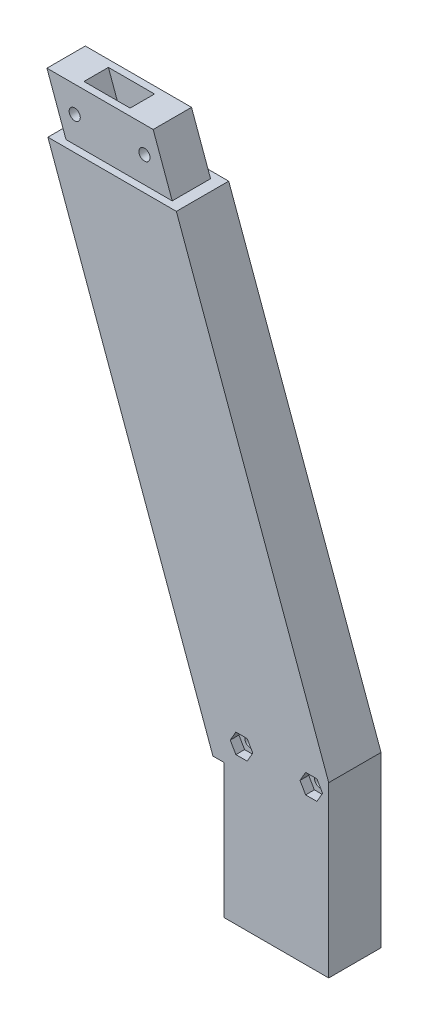
SolidWorks part; units mm, degrees
ref_plane "Front Plane" through (0, 0, 0) normal (0, 0, 1) x (1, 0, 0)
ref_plane "Top Plane" through (0, 0, 0) normal (0, 1, 0) x (1, 0, 0)
ref_plane "Right Plane" through (0, 0, 0) normal (1, 0, 0) x (0, 0, -1)
sketch "Sketch3" plane through (0, 0, 0) normal (0, 0, 1) x (1, 0, 0)
  line L1 (-127.0377, 609.9404) -> (92.9623, 609.9404)
  line L2 (-127.0377, 609.9404) -> (-127.0377, 389.9404)
  line L3 (-127.0377, 389.9404) -> (92.9623, 389.9404)
  line L4 (92.9623, 609.9404) -> (92.9623, 389.9404)
  dimension "D1" = 220
  dimension "D2" = 220
sketch "Sketch1" plane through (0, 0, 0) normal (0, 0, 1) x (1, 0, 0)
  line L0 (5, 40.95) -> (25, 40.95)
  line L1 (0, 0) -> (30, 0)
  line L2 (0, 0) -> (0, 34.5)
  line L3 (0, 34.5) -> (30, 34.5)
  line L4 (30, 0) -> (30, 34.5)
  line L5 (0, 0) -> (30, 0)
  line L6 (0, 0) -> (0, -4)
  line L7 (0, -4) -> (30, -4)
  line L8 (30, 0) -> (30, -4)
  line L9 (0, 34.5) -> (30, 34.5)
  line L10 (0, 34.5) -> (0, 44.5)
  line L11 (0, 44.5) -> (30, 44.5)
  line L12 (30, 34.5) -> (30, 44.5)
  line L14 (8.2332, 40.95) -> (6.6166, 43.75)
  line L15 (6.6166, 43.75) -> (3.3834, 43.75)
  line L16 (3.3834, 43.75) -> (1.7668, 40.95)
  line L17 (1.7668, 40.95) -> (3.3834, 38.15)
  line L18 (3.3834, 38.15) -> (6.6166, 38.15)
  line L19 (6.6166, 38.15) -> (8.2332, 40.95)
  line L20 (21.7668, 40.95) -> (23.3834, 38.15)
  line L21 (23.3834, 38.15) -> (26.6166, 38.15)
  line L22 (26.6166, 38.15) -> (28.2332, 40.95)
  line L23 (28.2332, 40.95) -> (26.6166, 43.75)
  line L24 (26.6166, 43.75) -> (23.3834, 43.75)
  line L25 (23.3834, 43.75) -> (21.7668, 40.95)
  circle A0 centre (15, 8) radius 6.5
  circle A1 centre (5, 40.95) radius 1.55
  circle A2 centre (25, 40.95) radius 1.55
  circle A3 centre (5, 40.95) radius 2.8 construction
  circle A4 centre (25, 40.95) radius 2.8 construction
  point P10 (15, 0)
  point P16 (5, 42.5)
  point P17 (5, 39.4)
  point P18 (15, 40.95)
  point P19 (15, 34.5)
  dimension "D4" = 13
  dimension "D7" = 3.1
  dimension "D10" = 5.6
  dimension "D1" = 30
  dimension "D2" = 34.5
  dimension "D3" = 4
  dimension "D5" = 8
  dimension "D6" = 20
  dimension "D8" = 4.9
  dimension "D9" = 2
sketch "Sketch2" plane through (0, 0, 0) normal (0, 0, 1) x (1, 0, 0)
  line L0 (0, 34.5) -> (-53.8676, 182.5)
  line L1 (-53.8676, 182.5) -> (-53.8676, 34.5)
  line L2 (-53.8676, 34.5) -> (0, 34.5)
  line L3 (30, 44.5) -> (-82.8834, 354.6447)
  line L4 (-82.8834, 354.6447) -> (-119.7157, 354.6447)
  line L5 (-119.7157, 354.6447) -> (-3.1925, 34.5)
  line L6 (-53.8676, 182.5) -> (-115.4312, 351.6447)
  line L7 (-55.9682, 179.5) -> (-19.136, 179.5)
  line L8 (-50.5087, 164.5) -> (-13.6764, 164.5)
  line L9 (-44.8223, 172) -> (-24.8223, 172)
  line L10 (-24.8223, 168.7668) -> (-22.0223, 170.3834)
  line L11 (-22.0223, 170.3834) -> (-22.0223, 173.6166)
  line L12 (-22.0223, 173.6166) -> (-24.8223, 175.2332)
  line L13 (-24.8223, 175.2332) -> (-27.6223, 173.6166)
  line L14 (-27.6223, 173.6166) -> (-27.6223, 170.3834)
  line L15 (-27.6223, 170.3834) -> (-24.8223, 168.7668)
  line L16 (-44.8223, 168.7668) -> (-42.0223, 170.3834)
  line L17 (-42.0223, 170.3834) -> (-42.0223, 173.6166)
  line L18 (-42.0223, 173.6166) -> (-44.8223, 175.2332)
  line L19 (-44.8223, 175.2332) -> (-47.6223, 173.6166)
  line L20 (-47.6223, 173.6166) -> (-47.6223, 170.3834)
  line L21 (-47.6223, 170.3834) -> (-44.8223, 168.7668)
  line L22 (-37.5521, 179.5) -> (-32.0925, 164.5)
  line L23 (-22.3285, 179.5) -> (-16.869, 164.5)
  line L24 (-52.7757, 179.5) -> (-47.3161, 164.5)
  line L25 (-44.1637, 179.5) -> (4.9723, 44.5)
  line L26 (0, 44.5) -> (30, 44.5) construction
  line L27 (-30.9405, 179.5) -> (18.1955, 44.5)
  line L28 (4.9723, 44.5) -> (18.1955, 44.5)
  line L29 (-44.1637, 179.5) -> (-30.9405, 179.5)
  line L30 (18.1955, 44.5) -> (30, 44.5)
  line L31 (4.9723, 44.5) -> (0, 44.5)
  line L32 (0, 44.5) -> (0, 34.5)
  circle A0 centre (-53.8676, 182.5) radius 2.5
  circle A1 centre (-66.1803, 216.3289) radius 2.5
  circle A2 centre (-78.493, 250.1579) radius 2.5
  circle A3 centre (-90.8058, 283.9868) radius 2.5
  circle A4 centre (-103.1185, 317.8157) radius 2.5
  circle A5 centre (-115.4312, 351.6447) radius 2.5
  circle A6 centre (-115.4312, 351.6447) radius 3
  circle A7 centre (-53.8676, 182.5) radius 3
  circle A8 centre (-24.8223, 172) radius 2.8 construction
  circle A9 centre (-44.8223, 172) radius 2.8 construction
  circle A10 centre (-44.8223, 172) radius 1.6
  circle A11 centre (-24.8223, 172) radius 1.6
  point P44 (-34.8223, 172)
  point P45 (-34.8223, 172)
  dimension "D3" = 5
  dimension "D5" = 6
  dimension "D8" = 5.6
  dimension "D10" = 3.2
  dimension "D1" = 148
  dimension "D2" = 70
  dimension "D6" = 180
  dimension "D7" = 15
  dimension "D9" = 20
  dimension "D11" = 3
  dimension "D12" = 3
  dimension "D13" = 12.4258
  dimension "D4" = 6
extrude "Boss-Extrude1" add sketch "Sketch1" along normal blind 15 contours L1 L4 L3 L2 A0 | L3 L12 L11 L10 L25 L24 L23 L22 L21 L20 L19 L18 L17 L16 L15 L14 | A0 | L8 L1 L6 L7 | A1 L14 L15 L16 L17 L18 L19 | A2 L20 L21 L22 L23 L24 L25 region at (7.3508, 39.5928, 0) region at (22.6492, 42.3072, 0) region at (15, 18.6108, 0) region at (15, -2, 0) region at (15, 39.1794, 0) region at (15, 8, 0)
extrude "Cut-Extrude2" cut sketch "Sketch1<3>" along normal blind 2 contours A0 region at (15, 8, 0)
sketch "Sketch1<3>" plane through (0, 0, 0) normal (0, 0, 1) x (1, 0, 0) same geometry as "Sketch1"
sketch "Sketch4" plane through (0, 0, 15) normal (0, 0, 1) x (1, 0, 0)
  line L1 (8.2332, 40.95) -> (6.6166, 43.75)
  line L2 (6.6166, 43.75) -> (3.3834, 43.75)
  line L3 (3.3834, 43.75) -> (1.7668, 40.95)
  line L4 (1.7668, 40.95) -> (3.3834, 38.15)
  line L5 (3.3834, 38.15) -> (6.6166, 38.15)
  line L6 (6.6166, 38.15) -> (8.2332, 40.95)
  line L7 (28.2332, 40.95) -> (26.6166, 43.75)
  line L8 (26.6166, 43.75) -> (23.3834, 43.75)
  line L9 (23.3834, 43.75) -> (21.7668, 40.95)
  line L10 (21.7668, 40.95) -> (23.3834, 38.15)
  line L11 (23.3834, 38.15) -> (26.6166, 38.15)
  line L12 (26.6166, 38.15) -> (28.2332, 40.95)
  circle A0 centre (5, 40.95) radius 2.8 construction
  circle A1 centre (25, 40.95) radius 2.8 construction
extrude "Cut-Extrude3" cut sketch "Sketch4" against normal blind 2.5
extrude "Boss-Extrude2" add sketch "Sketch2" along normal blind 15 contours L27 L30 L3 L8 | L25 L28 L27 L8 | L32 L31 L25 L8 L0 | L8 L5 L2 L0 region at (-25.2543, 99.5, 0) region at (-20.8265, 103.404, 0) region at (-10.2543, 104.5, 0) region at (2.2595, 104.5, 0)
extrude "Cut-Extrude4" cut sketch "Sketch2<3>" along normal offset from surface (11 mm away) 4 contours L25 L28 L27 L8 | L9 L25 L8 L22 | L7 L25 L9 L22 | L27 L7 L22 L9 | L27 L9 L22 L8 region at (-36.7632, 168.25, 0) region at (-10.2543, 104.5, 0) region at (-39.493, 175.75, 0) region at (-30.1516, 168.25, 0) region at (-32.8814, 175.75, 0) up to face at (-1.0539, 62.0714, 15)
sketch "Sketch2<3>" plane through (0, 0, 0) normal (0, 0, 1) x (1, 0, 0) same geometry as "Sketch2"
extrude "Boss-Extrude4" add sketch "Sketch2<5>" along normal offset from surface (13 mm away) 2 contours L25 L7 L0 L8 L9 L17 L16 L21 L20 L19 L18 | A10 L17 L18 L19 L20 L21 L16 | L25 L17 L9 | L9 L25 L8 L22 | L7 L25 L9 L22 | L27 L7 L22 L9 | L27 L9 L22 L8 | L7 L27 L9 L14 L13 L12 L11 L10 L15 L8 L23 | A11 L14 L15 L10 L11 L12 L13 | L9 L27 L14 region at (-49.8526, 172.0703, 0) region at (-36.7632, 168.25, 0) region at (-39.493, 175.75, 0) region at (-30.1516, 168.25, 0) region at (-41.8262, 172.5389, 0) region at (-32.8814, 175.75, 0) region at (-42.1079, 172.8083, 0) region at (-26.3584, 167.5121, 0) region at (-27.8185, 171.4611, 0) region at (-27.5368, 171.1917, 0) up to face at (-1.0539, 62.0714, 15)
sketch "Sketch2<5>" plane through (0, 0, 0) normal (0, 0, 1) x (1, 0, 0) same geometry as "Sketch2"
extrude "Cut-Extrude5" cut sketch "Sketch2<6>" along normal blind 2 contours L7 L27 L9 L14 L13 L12 L11 L10 L15 L8 L23 | L27 L9 L22 L8 | L9 L25 L8 L22 | L7 L25 L9 L22 | L27 L7 L22 L9 | L25 L7 L0 L8 L9 L17 L16 L21 L20 L19 L18 | A10 L17 L18 L19 L20 L21 L16 | L25 L17 L9 | A11 L14 L15 L10 L11 L12 L13 | L9 L27 L14 region at (-49.8526, 172.0703, 0) region at (-36.7632, 168.25, 0) region at (-39.493, 175.75, 0) region at (-30.1516, 168.25, 0) region at (-41.8262, 172.5389, 0) region at (-32.8814, 175.75, 0) region at (-42.1079, 172.8083, 0) region at (-26.3584, 167.5121, 0) region at (-27.8185, 171.4611, 0) region at (-27.5368, 171.1917, 0)
sketch "Sketch2<6>" plane through (0, 0, 0) normal (0, 0, 1) x (1, 0, 0) same geometry as "Sketch2"
extrude "Cut-Extrude6" cut sketch "Sketch2<7>" along normal offset from surface (11 mm away) 2 contours L7 L25 L9 L22 | L9 L25 L8 L22 | L27 L9 L22 L8 | L27 L7 L22 L9 region at (-36.7632, 168.25, 0) region at (-39.493, 175.75, 0) region at (-30.1516, 168.25, 0) region at (-32.8814, 175.75, 0) up to face at (-43.2223, 172, 13)
sketch "Sketch2<7>" plane through (0, 0, 0) normal (0, 0, 1) x (1, 0, 0) same geometry as "Sketch2"
extrude "Boss-Extrude8" add sketch "Sketch2<9>" along normal blind 4 contours L25 L28 L27 L8 region at (-10.2543, 104.5, 0)
sketch "Sketch2<9>" plane through (0, 0, 0) normal (0, 0, 1) x (1, 0, 0) same geometry as "Sketch2"
extrude "Boss-Extrude10" add sketch "Sketch2<11>" along normal offset from surface (4 mm away) 2 contours L9 L25 L8 L22 | L7 L25 L9 L22 | L27 L9 L22 L8 | L27 L7 L22 L9 region at (-36.7632, 168.25, 0) region at (-39.493, 175.75, 0) region at (-30.1516, 168.25, 0) region at (-32.8814, 175.75, 0) up to face at (-43.2223, 172, 2) offset beyond the face yes
sketch "Sketch2<11>" plane through (0, 0, 0) normal (0, 0, 1) x (1, 0, 0) same geometry as "Sketch2"
extrude "Cut-Extrude8" cut sketch "Sketch2<12>" along normal blind 2 contours L7 L25 L9 L22 | L9 L25 L8 L22 | L27 L9 L22 L8 | L27 L7 L22 L9 region at (-36.7632, 168.25, 0) region at (-39.493, 175.75, 0) region at (-30.1516, 168.25, 0) region at (-32.8814, 175.75, 0)
sketch "Sketch2<12>" plane through (0, 0, 0) normal (0, 0, 1) x (1, 0, 0) same geometry as "Sketch2"
sketch "Sketch6" plane through (0, 0, 0) normal (0, 0, -1) x (-1, 0, 0)
  line L0 (-18.1955, 44.5) -> (-4.9723, 44.5)
  line L1 (-4.9723, 44.5) -> (0.4873, 59.5)
  line L2 (44.1637, 179.5) -> (-4.9723, 44.5) construction
  line L3 (0.4873, 59.5) -> (-12.7359, 59.5)
  line L4 (30.9405, 179.5) -> (-18.1955, 44.5) construction
  line L5 (-12.7359, 59.5) -> (-18.1955, 44.5)
  dimension "D1" = 15
extrude "Cut-Extrude9" cut sketch "Sketch6" against normal up to next
